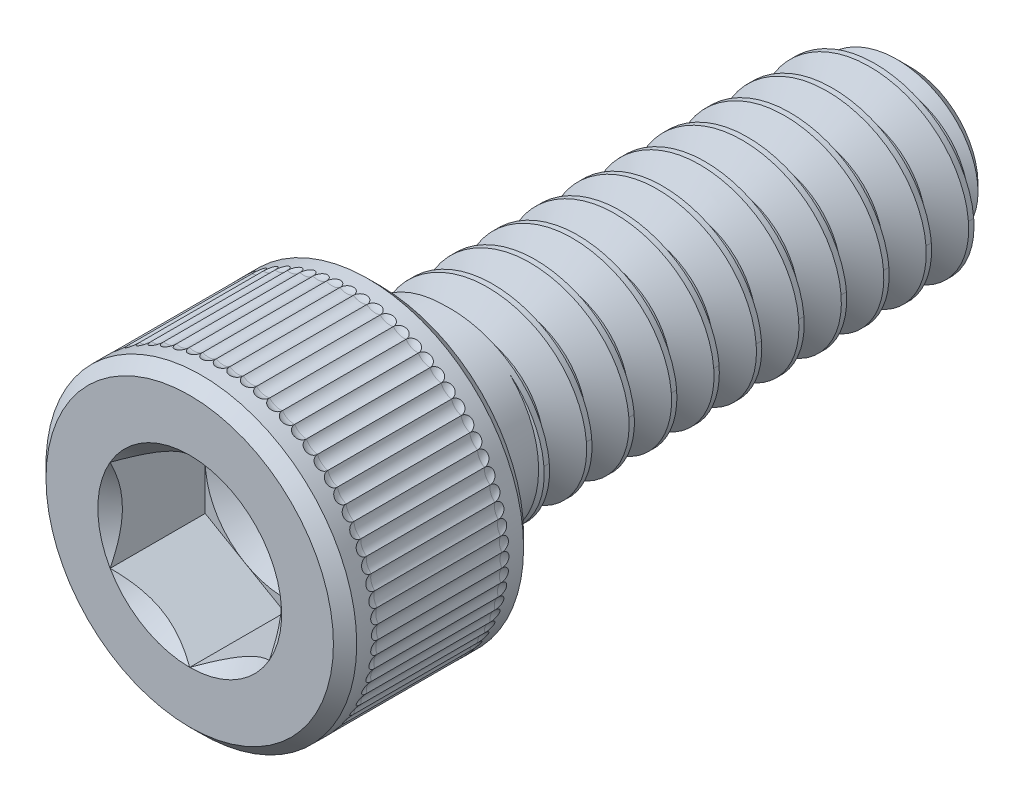
SolidWorks part; units mm, degrees
ref_plane "Front Plane" through (0, 0, 0) normal (0, 0, 1) x (1, 0, 0)
ref_plane "Top Plane" through (0, 0, 0) normal (0, 1, 0) x (1, 0, 0)
ref_plane "Right Plane" through (0, 0, 0) normal (1, 0, 0) x (0, 0, -1)
sketch "Sketch1" plane through (0, 0, 0) normal (1, 0, 0) x (0, 0, -1)
  line L0 (5.3911, 0) -> (-5.3911, 0) construction
  line L1 (-5.3911, -2.3241) -> (-5.3912, 2.3241) construction
  line L2 (-5.3912, 2.3241) -> (-2.5464, 2.3241) construction
  line L3 (5.3912, -1.4224) -> (5.3911, 1.4224) construction
  line L7 (5.3515, 1.4911) -> (5.9865, 1.4911) construction
  line L8 (5.9865, 1.4911) -> (5.669, 0.9412) construction
  line L9 (5.669, 0.9412) -> (5.3515, 1.4911) construction
  line L10 (5.669, 1.4911) -> (5.669, 1.4224) construction
  line L11 (5.669, 1.4224) -> (5.669, 1.01) construction
  line L12 (5.669, 1.01) -> (5.669, 0.9412) construction
  line L13 (5.6293, 1.01) -> (5.7086, 1.01) construction
  line L14 (5.3911, 1.4224) -> (5.9468, 1.4224) construction
  line L15 (5.3713, 1.4568) -> (5.9666, 1.4568) construction
  line L17 (5.3912, -1.4224) -> (3.8037, -1.4224) construction
  point P4 (0, 0)
  point P8 (-5.3911, 0)
  point P11 (5.3911, 0)
  point P16 (-5.3912, 1.1906)
  point P20 (5.669, 1.01)
  point P23 (5.669, 1.4224)
  point P26 (5.669, 1.4568)
  point P27 (-5.3912, -1.1906)
  dimension "Head Diameter" = 4.6482
  dimension "Head Height" = 2.8448
  dimension "Length" = 7.9375
  dimension "Screw Size Decimal Equivalent" = 2.8448
  dimension "Thread Pitch" = 0.635
  dimension "D1" = 0.0794
  dimension "Drive Size" = 2.3813
  dimension "D2" = 1.5875
sketch "Sketch2" plane through (0, 0, 0) normal (1, 0, 0) x (0, 0, -1)
  line L0 (-2.7207, 2.3241) -> (-2.5464, 2.1498)
  line L1 (-5.3912, 2.3241) -> (-2.5464, 2.3241) construction
  line L2 (-5.3912, 1.1906) -> (-3.9688, 1.1906)
  line L3 (-3.9688, 1.1906) -> (-3.9688, 0)
  line L4 (5.3911, 0) -> (-5.3911, 0) construction
  line L5 (-3.9688, 0) -> (5.3911, 0)
  line L6 (5.3911, 0) -> (5.3912, 1.01)
  line L7 (5.3912, -1.4224) -> (5.3912, 1.4224) construction
  line L8 (5.3912, 1.01) -> (4.9787, 1.4224)
  line L9 (4.9787, 1.4224) -> (-2.4041, 1.4224)
  line L10 (-2.5464, 1.5646) -> (-2.5464, 2.1498)
  line L11 (-5.3912, 1.1906) -> (-5.3911, 2.1498)
  line L12 (-5.3911, -2.3241) -> (-5.3911, 2.3241) construction
  line L13 (-5.3911, 2.1498) -> (-5.2168, 2.3241)
  line L14 (-5.2168, 2.3241) -> (-2.7207, 2.3241)
  arc A0 (-2.4041, 1.4224) -> (-2.5464, 1.5646) centre (-2.4041, 1.5646) cw
  point P24 (-2.5464, 1.4224)
  dimension "D6" = 0.1422
  dimension "D1" = 45
  dimension "D3" = 1.4224
  dimension "D4" = 45
  dimension "D5" = 0.1743
  dimension "D2" = 0.1743
revolve "Revolve1" add sketch "Sketch2" angle 360 about L5
sketch "Sketch3" plane through (0, 0, 5.3912) normal (0, 0, 1) x (1, 0, 0)
  line L5 (0, 1.3748) -> (-1.1906, 0.6874)
  line L7 (-1.1906, 0.6874) -> (-1.1906, -0.6874)
  line L8 (-1.1906, -0.6874) -> (0, -1.3748)
  line L9 (0, -1.3748) -> (1.1906, -0.6874)
  line L10 (1.1906, -0.6874) -> (1.1906, 0.6874)
  line L11 (1.1906, 0.6874) -> (0, 1.3748)
  circle A1 centre (0, 0) radius 1.1906 construction
  circle A2 centre (0, 0) radius 1.1906 construction
extrude "Cut-Extrude1" cut sketch "Sketch3" against normal up to surface (1.4224 mm away) up to face at (1.1906, 0, 3.9688)
sketch "Sketch4" plane through (0, 0, 5.3912) normal (0, 0, 1) x (1, 0, 0)
  circle A0 centre (0, 0) radius 1.3748
extrude "Cut-Extrude2" cut sketch "Sketch4" against normal through all draft 45
sketch "Sketch6" plane through (0, 0, 3.9688) normal (0, 0, 1) x (1, 0, 0)
  line L0 (-1.1906, 0.6874) -> (-1.1906, -0.6874) construction
  circle A1 centre (0, 0) radius 1.1906
extrude "Cut-Extrude5" cut sketch "Sketch6" against normal through all draft 60
sketch "Sketch7" plane through (0, 0, -5.3912) normal (0, 0, -1) x (-1, 0, 0)
  circle A0 centre (0, 0) radius 1.4224
curve "Helix/Spiral1" pitch 0.635 height 8.3344 turns 13.125
sketch "Sketch8" plane through (0, 0, 0) normal (1, 0, 0) x (0, 0, -1)
  line L0 (5.3713, 1.4568) -> (5.9666, 1.4568)
  line L1 (5.9666, 1.4568) -> (5.7086, 1.01)
  line L2 (5.7086, 1.01) -> (5.6293, 1.01)
  line L3 (5.6293, 1.01) -> (5.3713, 1.4568)
sweep "Cut-Sweep1" cut profiles "Sketch8" path "Helix/Spiral1"
sketch "Sketch9" plane through (0, 0, 0) normal (1, 0, 0) x (0, 0, -1)
  line L0 (-2.9829, 0) -> (-2.9829, 1.5646)
  line L1 (5.3911, 0) -> (-5.3911, 0) construction
  line L2 (-2.4041, 1.4224) -> (-1.5939, 1.4224)
  line L3 (-1.5939, 1.4224) -> (-0.7726, 0)
  line L4 (-0.7726, 0) -> (-2.9829, 0)
  line L5 (5.3911, 1.4224) -> (5.9468, 1.4224) construction
  line L8 (-3.9688, 0) -> (5.3911, 0) construction
  line L9 (5.3911, 0) -> (5.3911, 1.01) construction
  line L10 (-2.9829, 1.5646) -> (-2.5464, 1.5646)
  arc A0 (-2.5464, 1.5646) -> (-2.4041, 1.4224) centre (-2.4041, 1.5646) ccw construction
  arc A1 (-2.5464, 1.5646) -> (-2.4041, 1.4224) centre (-2.4041, 1.5646) ccw
  dimension "D1" = 60
  dimension "D3" = 8.3741
  dimension "D2" = 0.9525
revolve "Revolve2" add sketch "Sketch9" angle 360 about L4
ref_plane "Plane1" through (0, 0, 3.9688) normal (0, 0, -1) x (-1, 0, 0)
sketch "Sketch11" plane through (0, 0, 3.9688) normal (0, 0, -1) x (-1, 0, 0)
  line L0 (0, 0) -> (0.1014, 2.3219) construction
  line L1 (0.1014, 2.3219) -> (-0.1014, 2.3219) construction
  line L2 (-0.1014, 2.3219) -> (0, 0) construction
  line L3 (0.1014, 2.3219) -> (0, 2.2634) construction
  line L4 (0, 2.2634) -> (-0.1014, 2.3219) construction
  circle A0 centre (0, 2.4975) radius 0.2028
  circle A1 centre (0, 0) radius 2.3241 construction
  dimension "D1" = 5
  dimension "D2" = 120
sketch "Sketch12" plane through (0, 0, 0) normal (1, 0, 0) x (0, 0, -1)
  line L0 (-4.8933, 2.2947) -> (-3.0442, 2.2947)
  line L1 (-5.0961, 2.4975) -> (-2.8414, 2.4975)
  arc A0 (-3.0442, 2.2947) -> (-2.8414, 2.4975) centre (-3.0442, 2.4975) ccw
  arc A1 (-4.8933, 2.2947) -> (-5.0961, 2.4975) centre (-4.8933, 2.4975) cw
  point P3 (-3.9688, 2.4975)
  point P11 (-3.9688, 2.2947)
  dimension "D1" = 1.8491
revolve "Cut-Revolve1" cut sketch "Sketch12" angle 360 about L1
pattern_circular "CirPattern1" count 72 over 360 about axis through (0, 0, 0) along (0, 0, 1) of "Cut-Revolve1"
equation "\"D1@Sketch1\"=\"Thread Pitch@Sketch1\"/8"
equation "\"D5@Sketch2\"=\"D2@Sketch2\""
equation "\"D3@Helix/Spiral1\"=\"Length@Sketch1\"+\"Thread Pitch@Sketch1\"*0.625"
equation "\"D4@Helix/Spiral1\"=\"Thread Pitch@Sketch1\""
equation "\"D2@Sketch2\"=\"Head Diameter@Sketch1\"*0.0375"
equation "\"D2@Sketch1\"=\"Thread Pitch@Sketch1\"*2.5"
equation "\"D3@Sketch2\"=\"Head Height@Sketch1\"*0.5"
equation "\"60g\"=45"
equation "\"D6@Sketch2\" = \"Screw Size Decimal Equivalent@Sketch1\" * 0.05"
equation "\"D3@Sketch9\"=\"D3@Helix/Spiral1\"+\"D1@Sketch1\"*0.5"
equation "\"D2@Sketch9\"=\"Thread Pitch@Sketch1\"*1.5"
equation "\"D1\"= \"Head Height@Sketch1\" * 0.075"
equation "\"D1@Sketch12\"=\"Head Height@Sketch1\"*.65"
equation "\"D1@CirPattern1\"=360/\"D1@Sketch11\""
